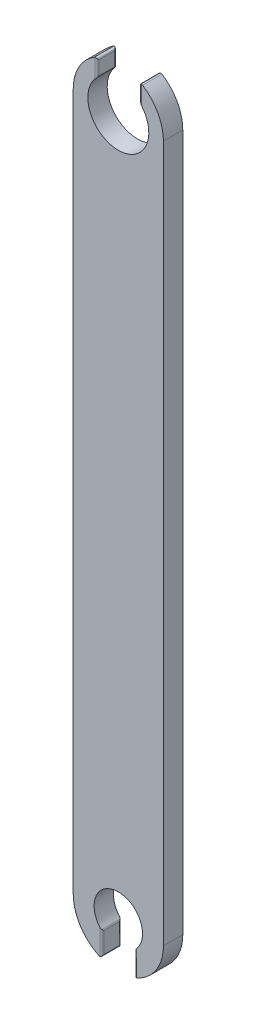
SolidWorks part; units mm, degrees
ref_plane "Front Plane" through (0, 0, 0) normal (0, 0, 1) x (1, 0, 0)
ref_plane "Top Plane" through (0, 0, 0) normal (0, 1, 0) x (1, 0, 0)
ref_plane "Right Plane" through (0, 0, 0) normal (1, 0, 0) x (0, 0, -1)
sketch "Sketch1" plane through (0, 0, 0) normal (0, 0, 1) x (1, 0, 0)
  line L0 (-5.9182, 5.5103) -> (-5.9182, 96.9503)
  line L1 (5.9182, 96.9503) -> (5.9182, 5.5103)
  line L2 (0, 0) -> (0, 102.0048) construction
  line L3 (-2.159, 3.1824) -> (-2.159, 0)
  line L4 (2.159, 3.1824) -> (2.159, 0)
  line L5 (-2.159, 3.1824) -> (2.159, 3.1824) construction
  line L6 (-2.794, 99.8128) -> (-2.794, 102.1675)
  line L7 (2.794, 102.1675) -> (2.794, 99.8128)
  line L8 (-2.794, 102.1675) -> (2.794, 102.1675) construction
  arc A0 (-5.9182, 96.9503) -> (-2.794, 102.1675) centre (0, 96.9503) cw
  arc A1 (5.9182, 5.5103) -> (2.159, 0) centre (0, 5.5103) cw
  arc A2 (-2.794, 99.8128) -> (2.794, 99.8128) centre (0, 96.9503) ccw
  arc A3 (2.159, 3.1824) -> (-2.159, 3.1824) centre (0, 5.5103) ccw
  arc A4 (-2.159, 0) -> (-5.9182, 5.5103) centre (0, 5.5103) cw
  arc A5 (2.794, 102.1675) -> (5.9182, 96.9503) centre (0, 96.9503) cw
  point P8 (0, 102.0048)
  point P16 (0, 0)
  point P19 (12.846, 99.8128)
  point P20 (0, 0)
  dimension "D1" = 5.9182
  dimension "D2" = 91.44
  dimension "D3" = 8
  dimension "D4" = 6.35
  dimension "D5" = 4.318
  dimension "D6" = 5.588
extrude "Boss-Extrude1" add sketch "Sketch1" along normal blind 2.54
fillet "Fillet1" radius 0.254 16 edges at (2.159, 3.1824, 1.27) (2.159, 1.5912, 2.54) (2.159, 0, 1.27) (2.159, 1.5912, 0) (-2.159, 0, 1.27) (-2.159, 1.5912, 2.54) (-2.159, 3.1824, 1.27) (-2.159, 1.5912, 0) (2.794, 102.1675, 1.27) (2.794, 100.9901, 2.54) (2.794, 99.8128, 1.27) (2.794, 100.9901, 0) (-2.794, 99.8128, 1.27) (-2.794, 100.9901, 2.54) (-2.794, 102.1675, 1.27) (-2.794, 100.9901, 0)
